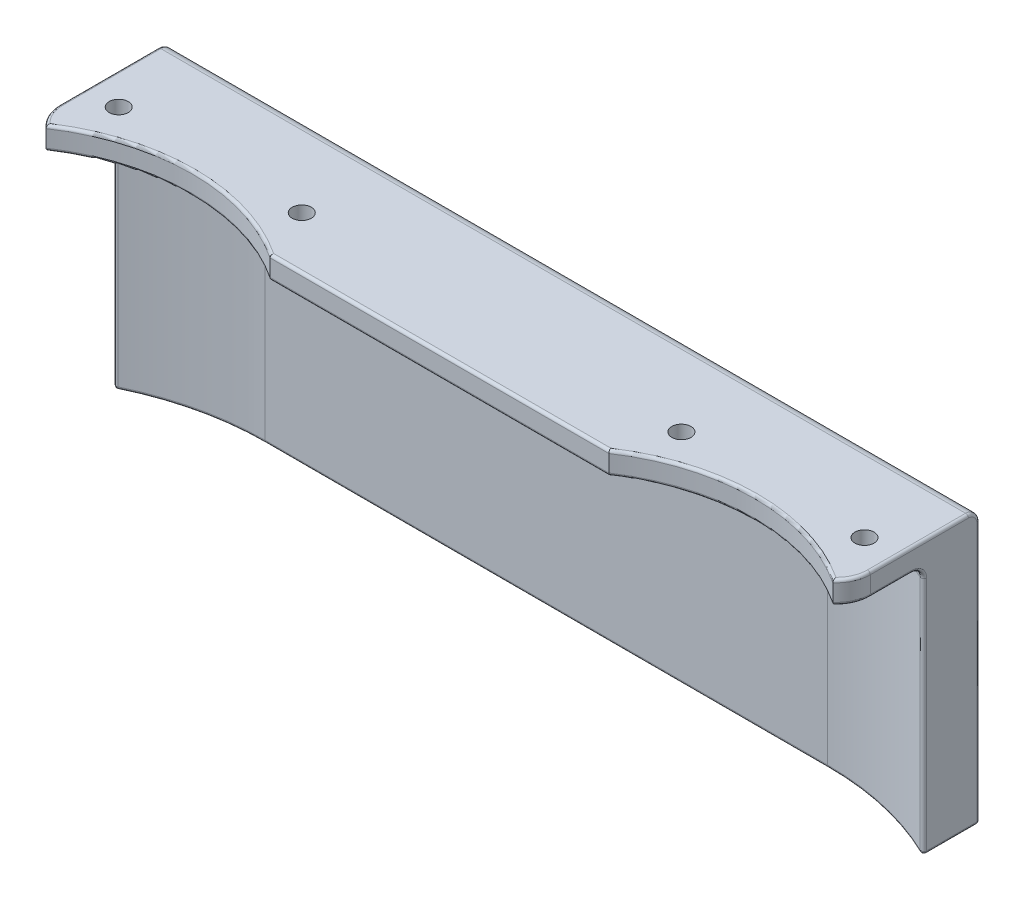
SolidWorks part; units mm, degrees
ref_plane "Front Plane" through (0, 0, 0) normal (0, 0, 1) x (1, 0, 0)
ref_plane "Top Plane" through (0, 0, 0) normal (0, 1, 0) x (1, 0, 0)
ref_plane "Right Plane" through (0, 0, 0) normal (1, 0, 0) x (0, 0, -1)
sketch "Sketch1" plane through (0, 0, 0) normal (0, 1, 0) x (1, 0, 0)
  circle A0 centre (-50, 0) radius 42.5 construction
  circle A1 centre (-50, 0) radius 49 construction
  circle A2 centre (50, 0) radius 49 construction
  circle A3 centre (50, 0) radius 42.5 construction
  circle A4 centre (-50, 0) radius 35.5 construction
  dimension "D1" = 85
  dimension "D2" = 98
  dimension "D5" = 71
  dimension "D3" = 50
  dimension "D4" = 50
sketch "Sketch2" plane through (0, 0, 0) normal (0, 1, 0) x (1, 0, 0)
  line L2 (72, 30) -> (72, 54)
  line L3 (-72, 54) -> (72, 54)
  line L4 (-30.1003, 30) -> (30.1003, 30)
  line L6 (69.8997, 30) -> (72, 30)
  line L7 (0, -55) -> (0, 55) construction
  line L8 (-69.8997, 30) -> (-72, 30)
  line L9 (-72, 30) -> (-72, 54)
  arc A1 (30.1003, 30) -> (69.8997, 30) centre (50, 0) cw
  arc A6 (-30.1003, 30) -> (-69.8997, 30) centre (-50, 0) ccw
  dimension "D2" = 54
  dimension "D3" = 36
  dimension "D1" = 30
  dimension "D4" = 72
extrude "Boss-Extrude1" add sketch "Sketch2" along normal blind 4
sketch "Sketch3" plane through (0, 0, 0) normal (0, -1, 0) x (1, 0, 0)
  line L0 (-72, -54) -> (-72, -30) construction
  line L1 (72, -54) -> (-72, -54)
  line L2 (72, -54) -> (72, -49)
  line L3 (72, -49) -> (-72, -49)
  line L4 (-72, -54) -> (-72, -49)
  dimension "D1" = 5
extrude "Boss-Extrude2" add sketch "Sketch3" along normal blind 44.5
sketch "Sketch5" plane through (0, 4, 0) normal (0, 1, 0) x (1, 0, 0)
  circle A0 centre (-66.264, 39.2649) radius 1.7
  circle A1 centre (-50, 0) radius 42.5 construction
  circle A2 centre (-33.736, 39.2649) radius 1.7
  circle A3 centre (33.736, 39.2649) radius 1.7
  circle A4 centre (50, 0) radius 42.5 construction
  circle A5 centre (66.264, 39.2649) radius 1.7
  dimension "D2" = 3.4
  dimension "D1" = 45
extrude "Cut-Extrude1" cut sketch "Sketch5" against normal up to surface (4 mm away) up to face at (0, 0, -36.25)
sketch "Sketch6" plane through (0, -44.5, 0) normal (0, -1, 0) x (1, 0, 0)
  line L0 (72, -49) -> (72, -43.7836)
  line L1 (72, -30) -> (72, -49) construction
  line L7 (50, 0) -> (50, -49) construction
  line L11 (72, -54) -> (72, -49) construction
  line L12 (72, -49) -> (50, -49)
  line L13 (0, -55) -> (0, 55) construction
  line L14 (-72, -49) -> (-50, -49)
  line L15 (-72, -49) -> (-72, -43.7836)
  arc A0 (50, -49) -> (72, -43.7836) centre (50, 0) ccw
  circle A1 centre (50, 0) radius 49 construction
  arc A3 (-50, -49) -> (-72, -43.7836) centre (-50, 0) cw
extrude "Boss-Extrude3" add sketch "Sketch6" against normal up to surface (44.5 mm away) up to face at (-66.264, 0, -40.9649)
fillet "Fillet1" radius 2 4 edges at (0, 0, -49) (0, 4, -54) (61.305, 0, -47.6781) (-61.305, 0, -47.6781)
fillet "Fillet2" radius 6 2 edges at (-72, 2, -30) (72, 2, -30)
fillet "Fillet3" radius 0.5 28 edges at (71.4497, 0, -32.0497) (72, 0, -38.0465) (0, -44.5, -49) (-71.4497, 0, -32.0497) (-71.4497, 4, -32.0497) (71.4497, 4, -32.0497) (72, 4, -43.2799) (72, 3.4142, -53.4142) (72, -21.25, -54) (0, -44.5, -54) (50, 4, -36) (50, 0, -36) (0, 4, -30) (0, 0, -30) (-50, 4, -36) (-50, 0, -36) (-72, 3.4142, -53.4142) (-72, 4, -43.2799) (-72, 0, -38.0465) (-72, -21.25, -54) (72, -0.5498, -43.0855) (72, -23.25, -43.7836) (61.305, -44.5, -47.6781) (-61.305, -44.5, -47.6781) (-72, -0.851, -43.3769) (-72, -23.25, -43.7836) (-72, -44.5, -48.8918) (72, -44.5, -48.8918)
